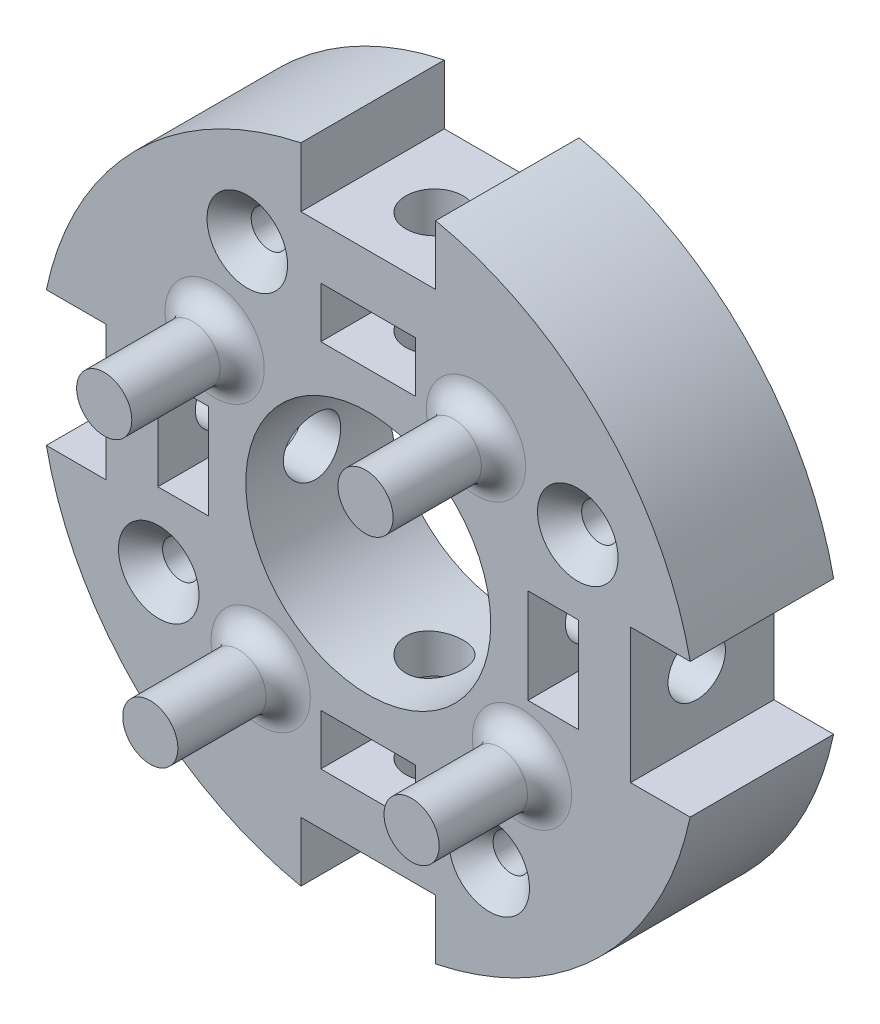
SolidWorks part; units mm, degrees
ref_plane "Plan de face" through (0, 0, 0) normal (0, 0, 1) x (1, 0, 0)
ref_plane "Plan de dessus" through (0, 0, 0) normal (0, 1, 0) x (1, 0, 0)
ref_plane "Plan de droite" through (0, 0, 0) normal (1, 0, 0) x (0, 0, -1)
sketch "Esquisse1" plane through (0, 0, 0) normal (0, 0, 1) x (1, 0, 0)
  line L1 (-29.4129, -5.9059) -> (-23.9629, -5.9059) construction
  line L3 (-29.4129, 5.9059) -> (-23.9629, 5.9059) construction
  line L4 (-23.9629, -5.9059) -> (-23.9629, 5.9059) construction
  line L5 (-29.4129, -5.9059) -> (-23.9629, 5.9059) construction
  line L6 (-29.4129, 5.9059) -> (-23.9629, -5.9059) construction
  line L7 (-5.9059, 29.4129) -> (-5.9059, 23.9629) construction
  line L8 (-5.9059, 23.9629) -> (5.9059, 23.9629) construction
  line L9 (5.9059, 29.4129) -> (5.9059, 23.9629) construction
  line L11 (29.4129, 5.9059) -> (23.9629, 5.9059) construction
  line L12 (23.9629, 5.9059) -> (23.9629, -5.9059) construction
  line L13 (29.4129, -5.9059) -> (23.9629, -5.9059) construction
  line L15 (5.9059, -29.4129) -> (5.9059, -23.9629) construction
  line L16 (5.9059, -23.9629) -> (-5.9059, -23.9629) construction
  line L17 (-5.9059, -29.4129) -> (-5.9059, -23.9629) construction
  line L18 (-6.1059, 29.1677) -> (-6.1059, 23.7629)
  line L19 (-6.1059, 23.7629) -> (6.1059, 23.7629)
  line L20 (6.1059, 29.1677) -> (6.1059, 23.7629)
  line L21 (29.1677, 6.1059) -> (23.7629, 6.1059)
  line L22 (23.7629, 6.1059) -> (23.7629, -6.1059)
  line L23 (29.1677, -6.1059) -> (23.7629, -6.1059)
  line L24 (6.1059, -29.1677) -> (6.1059, -23.7629)
  line L25 (6.1059, -23.7629) -> (-6.1059, -23.7629)
  line L26 (-6.1059, -29.1677) -> (-6.1059, -23.7629)
  line L27 (-29.1677, -6.1059) -> (-23.7629, -6.1059)
  line L28 (-23.7629, -6.1059) -> (-23.7629, 6.1059)
  line L29 (-29.1677, 6.1059) -> (-23.7629, 6.1059)
  line L30 (-4.3, 19.0629) -> (4.3, 19.0629)
  line L31 (-4, 18.7629) -> (4, 18.7629) construction
  line L32 (-4, 18.7629) -> (-4, 14.7629) construction
  line L33 (-4, 14.7629) -> (4, 14.7629) construction
  line L34 (4, 18.7629) -> (4, 14.7629) construction
  line L35 (-4, 18.7629) -> (4, 14.7629) construction
  line L36 (-4, 14.7629) -> (4, 18.7629) construction
  line L37 (4.3, 19.0629) -> (4.3, 14.4629)
  line L38 (-4.3, 14.4629) -> (4.3, 14.4629)
  line L39 (-4.3, 19.0629) -> (-4.3, 14.4629)
  line L40 (19.0629, 4.3) -> (19.0629, -4.3)
  line L41 (19.0629, -4.3) -> (14.4629, -4.3)
  line L42 (14.4629, 4.3) -> (14.4629, -4.3)
  line L43 (19.0629, 4.3) -> (14.4629, 4.3)
  line L44 (4.3, -19.0629) -> (-4.3, -19.0629)
  line L45 (-4.3, -19.0629) -> (-4.3, -14.4629)
  line L46 (4.3, -14.4629) -> (-4.3, -14.4629)
  line L47 (4.3, -19.0629) -> (4.3, -14.4629)
  line L48 (-19.0629, -4.3) -> (-19.0629, 4.3)
  line L49 (-19.0629, 4.3) -> (-14.4629, 4.3)
  line L50 (-14.4629, -4.3) -> (-14.4629, 4.3)
  line L51 (-19.0629, -4.3) -> (-14.4629, -4.3)
  line L52 (-0.2119, 0.3671) -> (-25000.2119, 43301.6373) construction
  line L54 (0, -1000) -> (0, 49000) construction
  arc A0 (-29.4129, -5.9059) -> (-5.9059, -29.4129) centre (0, 0) ccw construction
  circle A1 centre (0, 0) radius 11.1
  circle A2 centre (-10.9602, 18.9835) radius 1.65
  circle A3 centre (18.9835, 10.9602) radius 1.65
  circle A4 centre (10.9602, -18.9835) radius 1.65
  circle A5 centre (-18.9835, -10.9602) radius 1.65
  arc A6 (5.9059, -29.4129) -> (29.4129, -5.9059) centre (0, 0) ccw construction
  arc A7 (29.4129, 5.9059) -> (5.9059, 29.4129) centre (0, 0) ccw construction
  arc A8 (-5.9059, 29.4129) -> (-29.4129, 5.9059) centre (0, 0) ccw construction
  arc A9 (29.1677, 6.1059) -> (6.1059, 29.1677) centre (0, 0) ccw
  arc A10 (6.1059, -29.1677) -> (29.1677, -6.1059) centre (0, 0) ccw
  arc A11 (-29.1677, -6.1059) -> (-6.1059, -29.1677) centre (0, 0) ccw
  arc A12 (-6.1059, 29.1677) -> (-29.1677, 6.1059) centre (0, 0) ccw
  point P4 (-26.6879, 0)
  point P22 (0, 0)
  point P33 (0, 0)
  point P51 (0, 16.7629)
  point P56 (0, 23.7629)
  point P75 (0, 0)
  point P90 (0, 0)
  dimension "D1" = 60
  dimension "D2" = 22.2
  dimension "D7" = 3.3
  dimension "D3" = 5.45
  dimension "D4" = 4
  dimension "D5" = 21.9203
  dimension "D6" = 0.2
  dimension "D9" = 8
  dimension "D10" = 4
  dimension "D11" = 5
  dimension "D16" = 30
  dimension "D12" = 0.3
  dimension "D8" = 4
  dimension "D13" = 4
extrude "Boss.-Extru.1" add sketch "Esquisse1" along normal blind 13 contours A0 A1 A2 A3 | A0 A1 A5 A4 | A0 | A0 region at (-6.9309, 26.4653, 0)
chamfer "Chanfrein1" distance 2 angle 45 4 edges at (-17.3335, -10.9602, 13) (12.6102, -18.9835, 13) (20.6335, 10.9602, 13) (-9.3102, 18.9835, 13)
sketch "Esquisse6" plane through (-23.7629, 0, 0) normal (-1, 0, 0) x (0, 0, 1)
  line L1 (13, -6.1059) -> (13, 6.1059) construction
  circle A0 centre (7, 0) radius 2.6
  dimension "D1" = 5.2
  dimension "D2" = 6
extrude "Enlèv. mat.-Extru.4" cut sketch "Esquisse6" against normal blind 17
pattern_circular "Répétition circulaire1" count 4 over 360 about axis through (0, 0, 0) along (0, 0, 1) of "Enlèv. mat.-Extru.4"
sketch "Esquisse7" plane through (0, 0, 13) normal (0, 0, 1) x (1, 0, 0)
  line L0 (-1000, 0) -> (49000, 0) construction
  line L1 (0, 0) -> (-40957.6022, 28678.8218) construction
  circle A0 centre (-13.9256, 9.7508) radius 2.5
  circle A1 centre (9.7508, 13.9256) radius 2.5
  circle A2 centre (13.9256, -9.7508) radius 2.5
  circle A3 centre (-9.7508, -13.9256) radius 2.5
  point P16 (0, 0)
  dimension "D3" = 5
  dimension "D1" = 35
  dimension "D2" = 17
extrude "Boss.-Extru.2" add sketch "Esquisse7" along normal blind 10
fillet "Congé1" radius 2 4 edges at (16.4256, -9.7508, 13) (12.2508, 13.9256, 13) (-11.4256, 9.7508, 13) (-7.2508, -13.9256, 13)
